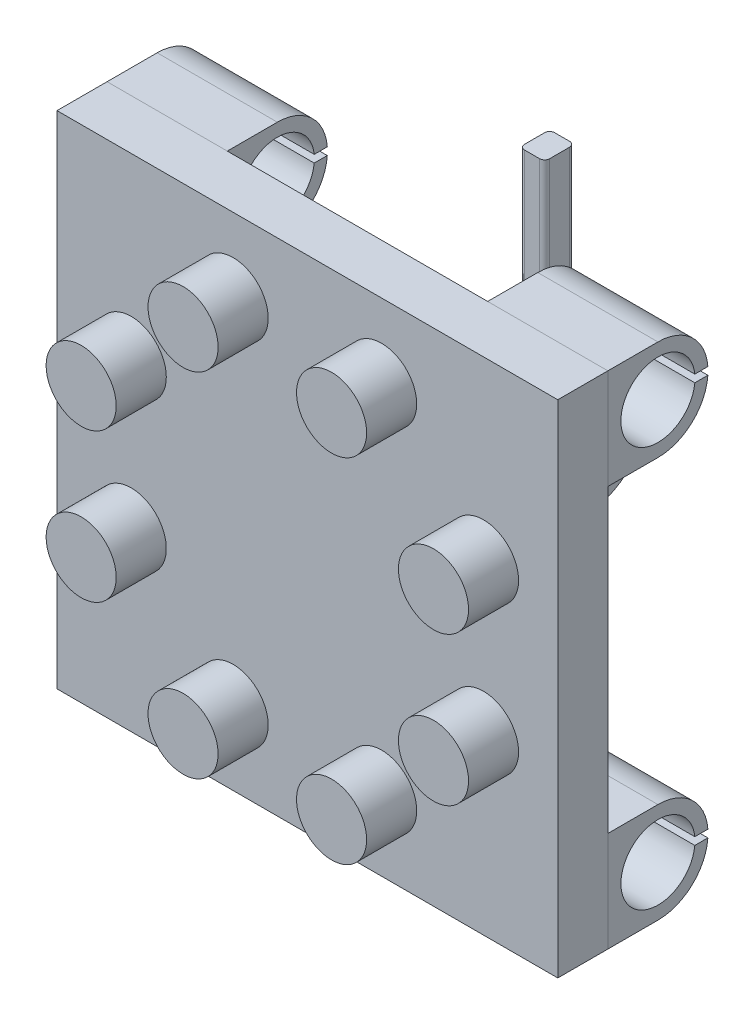
SolidWorks part; units mm, degrees
ref_plane "Plano frontal" through (0, 0, 0) normal (0, 0, 1) x (1, 0, 0)
ref_plane "Plano superior" through (0, 0, 0) normal (0, 1, 0) x (1, 0, 0)
ref_plane "Plano direito" through (0, 0, 0) normal (1, 0, 0) x (0, 0, -1)
sketch "Esboço1" plane through (0, 0, 0) normal (0, 0, 1) x (1, 0, 0)
  line L1 (-25.8743, 34.174) -> (-25.8743, -39.4705) construction
  line L2 (-25.8743, 21.9595) -> (37.4155, 21.9595) construction
  line L3 (24.1257, -28.0405) -> (24.1257, 21.9595) construction
  line L4 (-25.8743, 21.9595) -> (-11.0487, 7.134) construction
  line L5 (-11.0487, 7.134) -> (9.3002, -13.2149) construction
  line L6 (9.3002, -13.2149) -> (24.1257, -28.0405) construction
  line L7 (-25.8743, -28.0405) -> (24.1257, 21.9595) construction
  line L9 (-25.8743, 21.9595) -> (24.1257, 21.9595)
  line L10 (-25.8743, 21.9595) -> (-25.8743, -28.0405)
  line L11 (-25.8743, -28.0405) -> (24.1257, -28.0405)
  line L12 (24.1257, 21.9595) -> (24.1257, -28.0405)
  dimension "D1" = 50
extrude "Ressalto-extrusão1" add sketch "Esboço1" along normal blind 10
sketch "Esboço2" plane through (0, 0, 10) normal (0, 0, 1) x (1, 0, 0)
  line L0 (-25.8743, -28.0405) -> (27.247, -28.0405) construction
  line L1 (-11.0487, 21.9595) -> (-11.0487, -28.0405) construction
  line L2 (24.1257, 21.9595) -> (-25.8743, 21.9595) construction
  line L3 (9.3002, 21.9595) -> (9.3002, -28.0405) construction
  line L4 (-25.8743, -28.0405) -> (-25.8743, 21.9595) construction
  line L5 (-25.8743, 7.134) -> (24.1257, 7.134) construction
  line L6 (24.1257, -28.0405) -> (24.1257, 21.9595) construction
  line L7 (-25.8743, -13.2149) -> (24.1257, -13.2149) construction
  circle A0 centre (-11.0487, 7.134) radius 7
  circle A3 centre (9.3002, -13.2149) radius 7
extrude "Ressalto-extrusão2" add sketch "Esboço2" along normal blind 10
mirror "Espelhar11" about plane through (-25.8743, 21.9595, 10) normal (1, 0, 0) of "Ressalto-extrusão2", "Ressalto-extrusão1"
mirror "Espelhar12" about plane through (-25.8743, -28.0405, 10) normal (0, 1, 0) of "Ressalto-extrusão2", "Ressalto-extrusão1"
mirror "Espelhar13" about plane through (-25.8743, -78.0405, 10) normal (-1, 0, 0) of "Espelhar12"
sketch "Esboço3" plane through (0, 0, 0) normal (0, 0, -1) x (-1, 0, 0)
  line L2 (-24.1257, -78.0405) -> (-0.1257, -78.0405)
  line L5 (-24.1257, -78.0405) -> (-24.1257, -58.0405)
  line L31 (-24.1257, -58.0405) -> (-0.1257, -58.0405)
  line L35 (-0.1257, -78.0405) -> (-0.1257, -58.0405)
  line L41 (51.8743, -78.0405) -> (75.8743, -78.0405)
  line L54 (51.8743, -78.0405) -> (51.8743, -58.0405)
  line L55 (51.8743, -58.0405) -> (75.8743, -58.0405)
  line L56 (75.8743, -78.0405) -> (75.8743, -58.0405)
  line L57 (51.8743, 1.9595) -> (75.8743, 1.9595)
  line L58 (51.8743, 1.9595) -> (51.8743, 21.9595)
  line L59 (51.8743, 21.9595) -> (75.8743, 21.9595)
  line L60 (75.8743, 1.9595) -> (75.8743, 21.9595)
  line L61 (-24.1257, 1.9595) -> (-0.1257, 1.9595)
  line L62 (-24.1257, 1.9595) -> (-24.1257, 21.9595)
  line L63 (-24.1257, 21.9595) -> (-0.1257, 21.9595)
  line L64 (-0.1257, 1.9595) -> (-0.1257, 21.9595)
  dimension "D1" = 24
  dimension "D2" = 20
extrude "Ressalto-extrusão3" add sketch "Esboço3" along normal blind 20 separate body
fillet "Filete3" radius 10 2 edges at (12.1257, -58.0405, -20) (12.1257, -78.0405, -20)
fillet "Filete4" radius 10 2 edges at (-63.8743, -58.0405, -20) (-63.8743, -78.0405, -20)
fillet "Filete5" radius 10 2 edges at (12.1257, 21.9595, -20) (12.1257, 1.9595, -20)
fillet "Filete6" radius 10 2 edges at (-63.8743, 21.9595, -20) (-63.8743, 1.9595, -20)
sketch "Esboço4" plane through (24.1257, 0, 0) normal (1, 0, 0) x (0, 0, -1)
  line L0 (20, -68.0405) -> (17.4, -68.0405) construction
  line L1 (0, -58.0405) -> (0, -78.0405) construction
  line L2 (10, -78.0405) -> (10, -58.0405) construction
  line L3 (10, 1.9595) -> (10, 21.9595) construction
  line L4 (20, 11.9595) -> (0, 11.9595) construction
  line L5 (0, 21.9595) -> (0, 1.9595) construction
  line L6 (16.8497, -68.0405) -> (0, -68.0405) construction
  line L11 (20.3514, -68.7905) -> (17.3619, -68.7905)
  line L12 (20.3514, -68.7905) -> (20.3514, -67.2905)
  line L13 (20.3514, -67.2905) -> (17.3619, -67.2905)
  line L15 (20.3514, 11.2095) -> (17.3619, 11.2095)
  line L16 (20.3514, 11.2095) -> (20.3514, 12.7095)
  line L17 (20.3514, 12.7095) -> (17.3619, 12.7095)
  arc A0 (17.3619, -67.2905) -> (17.3619, -68.7905) centre (10, -68.0405) ccw
  arc A2 (17.3619, 12.7095) -> (17.3619, 11.2095) centre (10, 11.9595) ccw
  point P25 (10, 11.9595)
  dimension "D1" = 14.8
  dimension "D2" = 1.5
extrude "Corte-extrusão1" cut sketch "Esboço4" against normal through all both and the other way through all
sketch "Esboço5" plane through (0, 0, 0) normal (0, 0, -1) x (-1, 0, 0)
  line L0 (75.8743, -28.0405) -> (-24.1257, -28.0405) construction
  line L1 (75.8743, -78.0405) -> (75.8743, 21.9595) construction
  line L2 (-24.1257, -78.0405) -> (-24.1257, 21.9595) construction
  line L3 (25.8743, -78.0405) -> (25.8743, 21.9595) construction
  line L4 (-24.1257, -78.0405) -> (75.8743, -78.0405) construction
  line L5 (-24.1257, 21.9595) -> (75.8743, 21.9595) construction
  line L6 (43.3743, -28.0405) -> (8.3743, -28.0405) construction
  line L7 (43.3743, -43.0405) -> (8.3743, -43.0405)
  line L8 (43.3743, -43.0405) -> (43.3743, -13.0405)
  line L9 (43.3743, -13.0405) -> (8.3743, -13.0405)
  line L10 (8.3743, -43.0405) -> (8.3743, -13.0405)
  line L11 (25.8743, -43.0405) -> (25.8743, -13.0405) construction
  point P20 (25.8743, -28.0405)
  point P21 (25.8743, -28.0405)
  dimension "D1" = 35
  dimension "D2" = 30
extrude "Ressalto-extrusão4" add sketch "Esboço5" along normal blind 50
sketch "Esboço6" plane through (-43.3743, 0, 0) normal (-1, 0, 0) x (0, 0, 1)
  line L0 (-50, -28.0405) -> (0, -28.0405) construction
  line L1 (-50, -43.0405) -> (-50, -13.0405) construction
  line L2 (0, -78.0405) -> (0, 21.9595) construction
  line L3 (-25, -43.0405) -> (-25, -13.0405) construction
  line L4 (-50, -43.0405) -> (0, -43.0405) construction
  line L5 (-50, -13.0405) -> (0, -13.0405) construction
  line L6 (-25, -43.0405) -> (-50, -13.0405) construction
  line L7 (-25, -13.0405) -> (-50, -43.0405) construction
  circle A0 centre (-37.5, -28.0405) radius 11.5
  dimension "D1" = 23
sketch "Esboço7" plane through (0, -43.0405, 0) normal (0, -1, 0) x (1, 0, 0)
  line L0 (-25.8743, -50) -> (-25.8743, 0) construction
  line L1 (-8.3743, -50) -> (-43.3743, -50) construction
  line L2 (-8.3743, 0) -> (-43.3743, 0) construction
  line L3 (-25.8743, -50) -> (-32.8743, -50) construction
  line L4 (-25.8743, -50) -> (-18.8743, -50) construction
  line L5 (-8.3743, 0) -> (-8.3743, -50)
  line L6 (-18.8743, -50) -> (-8.3743, -50)
  line L7 (-43.3743, 0) -> (-43.3743, -50)
  line L8 (-32.8743, -50) -> (-43.3743, -50)
  arc A0 (-32.8743, -50) -> (-43.3743, 0) centre (-157.1719, -50) ccw
  arc A1 (-18.8743, -50) -> (-8.3743, 0) centre (105.4234, -50) cw
extrude "Corte-extrusão2" cut sketch "Esboço7" against normal through all both and the other way through all
extrude "Corte-extrusão3" cut sketch "Esboço6" against normal blind 15
sketch "Esboço8" plane through (-28.3743, 0, 0) normal (-1, 0, 0) x (0, 0, 1)
  circle A0 centre (-37.5, -28.0405) radius 5.25
  circle A1 centre (-37.5, -28.0405) radius 11.5 construction
  dimension "D1" = 10.5
extrude "Corte-extrusão4" cut sketch "Esboço8" against normal through all
fillet "Filete7" radius 10 2 edges at (-25.8743, -13.0405, -50) (-25.8743, -43.0405, -50)
sketch "Esboço9" plane through (0, -13.0405, 0) normal (0, 1, 0) x (1, 0, 0)
  line L0 (-175.2445, 37.8701) -> (-15.7518, 37.8701) construction
  line L1 (-27.3743, 40.8701) -> (-24.3743, 40.8701)
  line L2 (-28.3743, 39.8701) -> (-28.3743, 35.8701)
  line L3 (-27.3743, 34.8701) -> (-24.3743, 34.8701)
  line L4 (-23.3743, 39.8701) -> (-23.3743, 35.8701)
  line L5 (-28.3743, 37.8701) -> (-23.3743, 37.8701) construction
  line L6 (-25.8743, 50) -> (-25.8743, 23.4143) construction
  line L7 (-32.8743, 50) -> (-18.8743, 50) construction
  line L8 (-25.8743, 40.8701) -> (-25.8743, 34.8701) construction
  arc A0 (-28.3743, 35.8701) -> (-27.3743, 34.8701) centre (-27.3743, 35.8701) ccw
  arc A1 (-24.3743, 34.8701) -> (-23.3743, 35.8701) centre (-24.3743, 35.8701) ccw
  arc A2 (-24.3743, 40.8701) -> (-23.3743, 39.8701) centre (-24.3743, 39.8701) cw
  arc A3 (-27.3743, 40.8701) -> (-28.3743, 39.8701) centre (-27.3743, 39.8701) ccw
  point P19 (-23.3743, 34.8701)
  point P22 (-23.3743, 40.8701)
  point P25 (-28.3743, 40.8701)
  dimension "D3" = 1
  dimension "D1" = 5
  dimension "D2" = 6
extrude "Ressalto-extrusão5" add sketch "Esboço9" along normal blind 30
